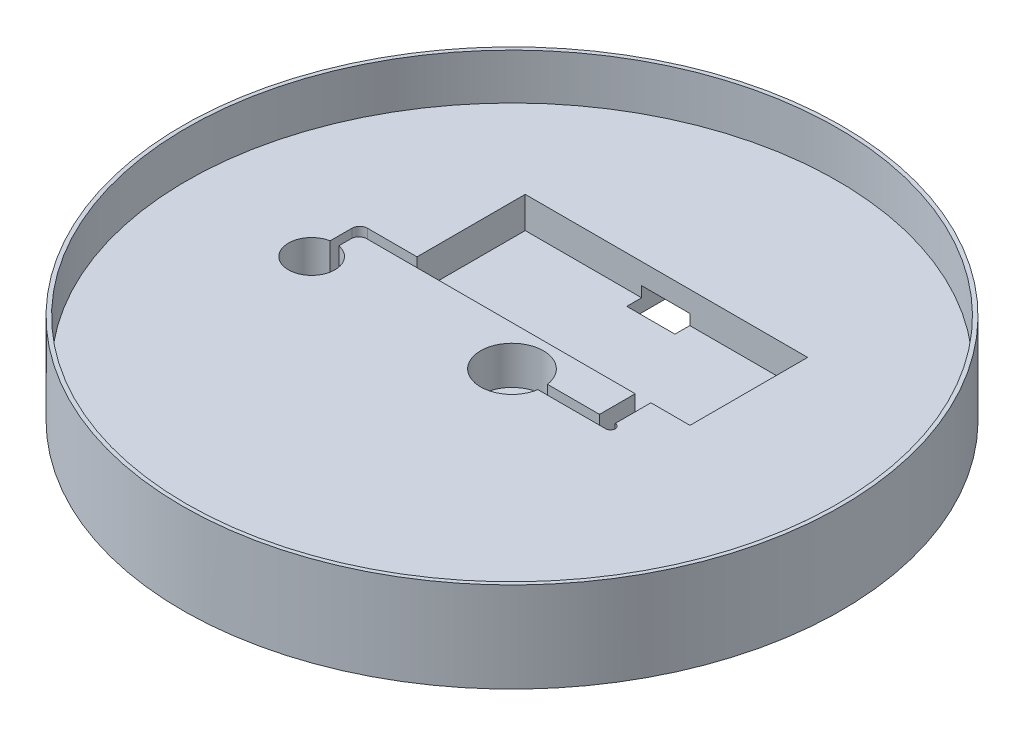
SolidWorks part; units mm, degrees
ref_plane "Front Plane" through (0, 0, 0) normal (0, 0, 1) x (1, 0, 0)
ref_plane "Top Plane" through (0, 0, 0) normal (0, 1, 0) x (1, 0, 0)
ref_plane "Right Plane" through (0, 0, 0) normal (1, 0, 0) x (0, 0, -1)
sketch "Sketch1" plane through (0, 0, 0) normal (0, 1, 0) x (1, 0, 0)
  circle A0 centre (0, 0) radius 266.7
extrude "Boss-Extrude1" add sketch "Sketch1" along normal blind 73.025
sketch "Sketch2" plane through (0, 73.025, 0) normal (0, 1, 0) x (1, 0, 0)
  circle A0 centre (0, 0) radius 263.525
extrude "Cut-Extrude1" cut sketch "Sketch2" against normal blind 37.084
sketch "Sketch3" plane through (0, 35.941, 0) normal (0, 1, 0) x (1, 0, 0)
  circle A0 centre (0, 0) radius 25.4
extrude "Cut-Extrude2" cut sketch "Sketch3" against normal blind 30.988
sketch "Sketch4" plane through (0, 35.941, 0) normal (0, 1, 0) x (1, 0, 0)
  line L0 (3.81, -0.2983) -> (80.01, -0.2983) construction
  line L1 (0, 3.5117) -> (76.2, 3.5117) construction
  line L2 (0, 3.5117) -> (0, -4.1083) construction
  line L3 (0, -4.1083) -> (76.2, -4.1083) construction
  line L4 (76.2, 3.5117) -> (76.2, -4.1083) construction
  line L5 (3.81, 3.5117) -> (80.01, 3.5117)
  line L6 (3.81, -4.1083) -> (80.01, -4.1083)
  line L7 (0, 3.5117) -> (0, -4.1083) construction
  arc A0 (3.81, 3.5117) -> (3.81, -4.1083) centre (3.81, -0.2983) ccw
  arc A1 (80.01, -4.1083) -> (80.01, 3.5117) centre (80.01, -0.2983) ccw
  point P6 (41.91, -0.2983)
extrude "Cut-Extrude3" cut sketch "Sketch4" against normal through all
sketch "Sketch15" plane through (0, 35.941, 0) normal (0, 1, 0) x (1, 0, 0)
  line L1 (-156.3248, 16.1533) -> (-156.3248, 18.4792)
  line L3 (-163.3516, 16.1533) -> (-163.3516, 18.4792)
  line L4 (-156.3248, 18.4792) -> (-163.3516, 18.4792)
  circle A0 centre (0, 0) radius 177.8 construction
  circle A1 centre (-159.4109, -0.0658) radius 16.9418 construction
  arc A2 (-163.3516, 16.1533) -> (-156.3248, 16.1533) centre (-159.8382, -2.3115) ccw
  point P6 (-159.8382, -2.3115)
extrude "Cut-Extrude12" cut sketch "Sketch15" against normal blind 27.94
sketch "Sketch19" plane through (0, 35.941, 0) normal (0, 1, 0) x (1, 0, 0)
  line L0 (80.01, 3.5117) -> (80.01, 32.4082)
  line L1 (-116.966, 32.4082) -> (67.31, 32.4082)
  line L2 (111.634, 32.4082) -> (111.634, 127.6582)
  line L3 (111.634, 127.6582) -> (-116.966, 127.6582)
  line L4 (-116.966, 127.6582) -> (-116.966, 32.4082)
  line L5 (80.01, 32.4082) -> (111.634, 32.4082)
  line L6 (67.31, 32.4082) -> (67.31, 3.5117)
  line L7 (80.01, 3.5117) -> (25.1561, 3.5117) construction
  line L8 (67.31, 3.5117) -> (80.01, 3.5117)
  circle A0 centre (0, 0) radius 263.525 construction
  circle A1 centre (0, 0) radius 177.7946 construction
extrude "Cut-Extrude13" cut sketch "Sketch19" against normal blind 25.4
sketch "Sketch20" plane through (0, 35.941, 0) normal (0, 1, 0) x (1, 0, 0)
  line L0 (-116.966, 32.4082) -> (-149.9748, 32.4082)
  line L1 (-156.3248, 26.0582) -> (-156.3248, 18.4792)
  line L2 (-156.3248, 18.4792) -> (-163.3516, 18.4792)
  line L3 (-163.3516, 18.4792) -> (-163.3516, 33.7217)
  line L4 (-157.0016, 40.0717) -> (-116.966, 40.0717)
  line L5 (-116.966, 127.6582) -> (-116.966, 32.4082) construction
  line L6 (-116.966, 40.0717) -> (-116.966, 32.4082)
  arc A0 (-157.0016, 40.0717) -> (-163.3516, 33.7217) centre (-157.0016, 33.7217) ccw
  arc A1 (-156.3248, 26.0582) -> (-149.9748, 32.4082) centre (-149.9748, 26.0582) cw
  dimension "D1" = 6.35
  dimension "D2" = 6.35
extrude "Cut-Extrude14" cut sketch "Sketch20" against normal blind 25.4
sketch "Sketch21" plane through (0, 0, 0) normal (0, -1, 0) x (-1, 0, 0)
  line L0 (22.7656, 115.6391) -> (-16.229, 115.6391) construction
  line L1 (-16.229, 115.6391) -> (-16.229, 283.8607)
  line L2 (-16.229, 283.8607) -> (22.7656, 283.8607)
  line L3 (22.7656, 283.8607) -> (22.7656, 115.6391)
  line L4 (22.7656, 115.6391) -> (-16.229, 115.6391)
extrude "Cut-Extrude15" cut sketch "Sketch21" against normal blind 19.05
